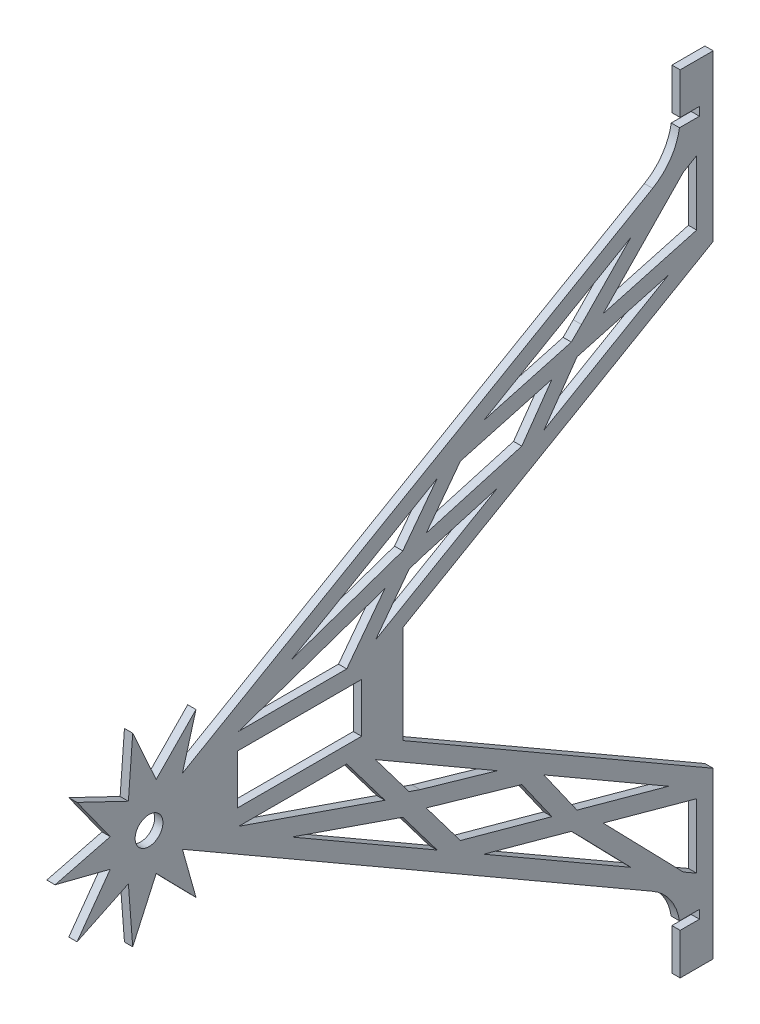
SolidWorks part; units mm, degrees
ref_plane "Front Plane" through (0, 0, 0) normal (1, 0, 0) x (0, 1, 0)
ref_plane "Top Plane" through (0, 0, 0) normal (0, 0, 1) x (0, 1, 0)
ref_plane "Right Plane" through (0, 0, 0) normal (0, 1, 0) x (-1, 0, 0)
sketch "Sketch1" plane through (0, 0, 0) normal (1, 0, 0) x (0, 1, 0)
  line L0 (-4.95, 0) -> (-129.0803, -215) construction
  line L1 (0, -4.95) -> (-121.2724, -215) construction
  line L2 (0, -4.95) -> (121.2724, -215) construction
  line L3 (4.95, 0) -> (129.0803, -215) construction
  line L4 (0, 0) -> (0, -215) construction
  line L5 (-129.0803, -215) -> (129.0803, -215) construction
  line L6 (0, 0) -> (0, -38.94) construction
  line L7 (0, -38.94) -> (0, -77.24) construction
  line L8 (-8.95, -32.14) -> (8.95, -32.14)
  line L9 (-8.95, -32.14) -> (-8.95, -77.24)
  line L10 (-8.95, -77.24) -> (8.95, -77.24)
  line L11 (8.95, -32.14) -> (8.95, -77.24)
  line L12 (-10.8997, -10.3052) -> (-129.0803, -215)
  line L13 (-129.0803, -215) -> (-88.6658, -215)
  line L14 (-88.6658, -215) -> (-17.7903, -92.24)
  line L15 (-17.7903, -92.24) -> (17.7903, -92.24)
  line L16 (17.7903, -92.24) -> (88.6658, -215)
  line L17 (88.6658, -215) -> (129.0803, -215)
  line L18 (129.0803, -215) -> (10.8997, -10.3052)
  circle A0 centre (0, 0) radius 4.95 construction
  circle A1 centre (0, 0) radius 7.5 construction
  arc A2 (-10.8997, -10.3052) -> (10.8997, -10.3052) centre (0, 0) cw
  circle A3 centre (0, 0) radius 4.95
  dimension "D2" = 9.9
  dimension "D3" = 15
  dimension "D9" = 15
  dimension "D10" = 35
  dimension "D1" = 215
  dimension "D4" = 60
  dimension "D5" = 38.94
  dimension "D6" = 45.1
  dimension "D7" = 17.9
  dimension "D8" = 6.8
  dimension "D11" = 35
  dimension "D12" = 15
extrude "Boss-Extrude1" add sketch "Sketch1" along normal blind 3
sketch "Sketch2" plane through (3, 0, 0) normal (1, 0, 0) x (0, 1, 0)
  line L1 (-129.0803, -215) -> (129.0803, -215)
  line L2 (-129.0803, -215) -> (-129.0803, -205)
  line L3 (-129.0803, -205) -> (129.0803, -205)
  line L4 (129.0803, -215) -> (129.0803, -205)
  dimension "D1" = 10
extrude "Cut-Extrude1" cut sketch "Sketch2" against normal through all both and the other way through all
sketch "Sketch3" plane through (3, 0, 0) normal (1, 0, 0) x (0, 0, -1)
  line L1 (205, -82.8923) -> (193, -82.8923)
  line L2 (205, -82.8923) -> (205, -142.8923)
  line L3 (205, -142.8923) -> (193, -142.8923)
  line L4 (193, -82.8923) -> (193, -142.8923)
  line L5 (205, 82.8923) -> (193, 82.8923)
  line L6 (205, 82.8923) -> (205, 142.8923)
  line L7 (205, 142.8923) -> (193, 142.8923)
  line L8 (193, 82.8923) -> (193, 142.8923)
  dimension "D1" = 12
  dimension "D2" = 12
  dimension "D3" = 60
  dimension "D4" = 60
extrude "Boss-Extrude2" add sketch "Sketch3" against normal blind 3
fillet "Fillet1" radius 20 2 edges at (1.5, 116.3786, -193) (1.5, -116.3786, -193)
sketch "Sketch4" plane through (3, 0, 0) normal (1, 0, 0) x (0, 0, -1)
  line L0 (-7.5, 12.9904) -> (-14.0954, 5.1303) construction
  line L1 (-14.0954, -5.1303) -> (-7.5, -12.9904) construction
  line L2 (-7.5, -12.9904) -> (2.6047, -14.7721) construction
  line L3 (2.6047, -14.7721) -> (11.4907, -9.6418) construction
  line L4 (11.4907, -9.6418) -> (15, 0) construction
  line L5 (15, 0) -> (11.4907, 9.6418) construction
  line L6 (11.4907, 9.6418) -> (2.6047, 14.7721) construction
  line L7 (2.6047, 14.7721) -> (-7.5, 12.9904) construction
  line L8 (-14.0954, 5.1303) -> (-14.0954, -5.1303) construction
  line L9 (15, 0) -> (0, 0) construction
  line L10 (0, 0) -> (-14.0954, -5.1303) construction
  line L11 (0, 0) -> (-14.0954, 5.1303) construction
  line L12 (-14.0954, -5.1303) -> (-34.138, 0)
  line L13 (-34.138, 0) -> (-14.0954, 5.1303)
  line L14 (0, 0) -> (-14.0954, 0)
  line L15 (-14.0954, 0) -> (-34.138, 0)
  line L16 (-14.0954, -5.1303) -> (-14.0954, 5.1303)
  circle A0 centre (0, 0) radius 14.0954 construction
  arc A1 (10.3052, 10.8997) -> (10.3052, -10.8997) centre (0, 0) ccw construction
  arc M29 (10.3052, 10.8997) -> (10.3052, -10.8997) centre (0, 0) ccw
extrude "Boss-Extrude3" add sketch "Sketch4" against normal blind 3 contours L15 L13 M29 | L15 L12 M29 region at (3, -1.6958, 21.1835) region at (3, 1.6958, 21.1835)
ref_axis "Axis1" through (-0.1502, 0, 0) along (1, 0, 0)
pattern_circular "CirPattern1" count 9 over 360 about axis through (-0.1502, 0, 0) along (1, 0, 0) of "Boss-Extrude3"
sketch "Sketch5" plane through (3, 0, 0) normal (1, 0, 0) x (0, 0, -1)
  line L0 (205, -142.8923) -> (205, -82.8923) construction
  line L1 (200, -124.7923) -> (183, -124.7923)
  line L2 (200, -124.7923) -> (200, -127.8923)
  line L3 (200, -127.8923) -> (183, -127.8923)
  line L4 (183, -124.7923) -> (183, -127.8923)
  line L5 (193, -142.8923) -> (205, -142.8923) construction
  dimension "D1" = 5
  dimension "D2" = 22
  dimension "D3" = 15
  dimension "D4" = 3.1
extrude "Cut-Extrude2" cut sketch "Sketch5" against normal through all both and the other way through all
mirror "Mirror1" about plane through (0, 0, 0) normal (0, 1, 0) of "Cut-Extrude2"
sketch "Sketch6" plane through (3, 0, 0) normal (1, 0, 0) x (0, 1, 0)
  line L8 (-14.95, -75.6035) -> (-86.3564, -199)
  line L9 (-16.7578, -73.2093) -> (-15.4134, -72.1942)
  line L12 (-20.0419, -38.14) -> (-104.6051, -184.6077)
  line L18 (-40.452, -87.9788) -> (-41.913, -92.2033)
  line L19 (-16.7578, -73.2093) -> (-33.3206, -85.7154)
  line L20 (-68.2493, -121.6376) -> (-88.914, -196.9829)
  line L21 (-18.8134, -82.2798) -> (-34.9667, -94.4767)
  line L22 (-59.7005, -113.1525) -> (-68.825, -146.421)
  line L23 (-104.6051, -184.6077) -> (-112.9145, -199)
  line L24 (-102.2289, -186.4817) -> (-110.1106, -194.1434)
  line L25 (-88.914, -196.9829) -> (-89.4672, -199)
  line L26 (-102.2289, -186.4817) -> (-80.1463, -165.0151)
  line L27 (-68.3452, -153.4201) -> (-54.2342, -143.4901)
  line L28 (-44.4406, -126.5659) -> (-36.3741, -98.5461)
  line L29 (-27.9579, -51.8508) -> (-40.452, -87.9788)
  line L30 (-99.0996, -175.072) -> (-80.6727, -157.1591)
  line L31 (-68.825, -146.421) -> (-53.2438, -135.4564)
  line L32 (-53.2438, -135.4564) -> (-43.2459, -100.7281)
  line L33 (-19.1463, -44.7292) -> (-33.3206, -85.7154)
  line L34 (-20.0419, -38.14) -> (-14.95, -29.3407)
  line L35 (-36.3741, -98.5461) -> (-34.9667, -94.4767)
  line L36 (-68.3452, -153.4201) -> (-71.3184, -155.5124)
  line L37 (-80.6727, -157.1591) -> (-76.9784, -153.4648)
  line L38 (-71.3184, -155.5124) -> (-80.4428, -188.7809)
  line L39 (-41.913, -92.2033) -> (-58.4758, -104.7094)
  line L40 (-43.2459, -100.7281) -> (-59.7005, -113.1525)
  line L41 (-14.95, -75.6035) -> (-14.95, -29.3407)
  line L42 (-19.1463, -44.7292) -> (-14.95, -32.5951)
  line L43 (-15.4134, -72.1942) -> (-14.95, -71.8443)
  line L44 (-86.3564, -199) -> (-112.9145, -199)
extrude "Cut-Extrude3" cut sketch "Sketch6" against normal through all both and the other way through all contours L9 L43 L41 L42 L33 L19 | L39 L18 L29 L12 | L35 L28 L8 L21 | L32 L40 L22 L31 | L36 L38 L8 L27 | L30 L37 L20 L12 | L44 L25 L20 L26 L24 L23 region at (3, -32.8347, -101.1949) region at (3, -21.0735, -63.3849) region at (3, -68.6652, -162.5944) region at (3, -42.7822, -82.9212) region at (3, -94.6864, -187.5516) region at (3, -81.4577, -150.1016) region at (3, -56.1842, -123.8068)
fillet "Fillet2" [suppressed] radius 2
mirror "Mirror2" about plane through (0, 0, 0) normal (0, 1, 0) of "Cut-Extrude3"
sketch "Main_shaft_clearance_profile" plane through (0, 0, 0) normal (1, 0, 0) x (0, 1, 0)
  circle A0 centre (0, 0) radius 5.05
extrude "Shaft_clearance_10p1" cut sketch "Main_shaft_clearance_profile" along normal through all
